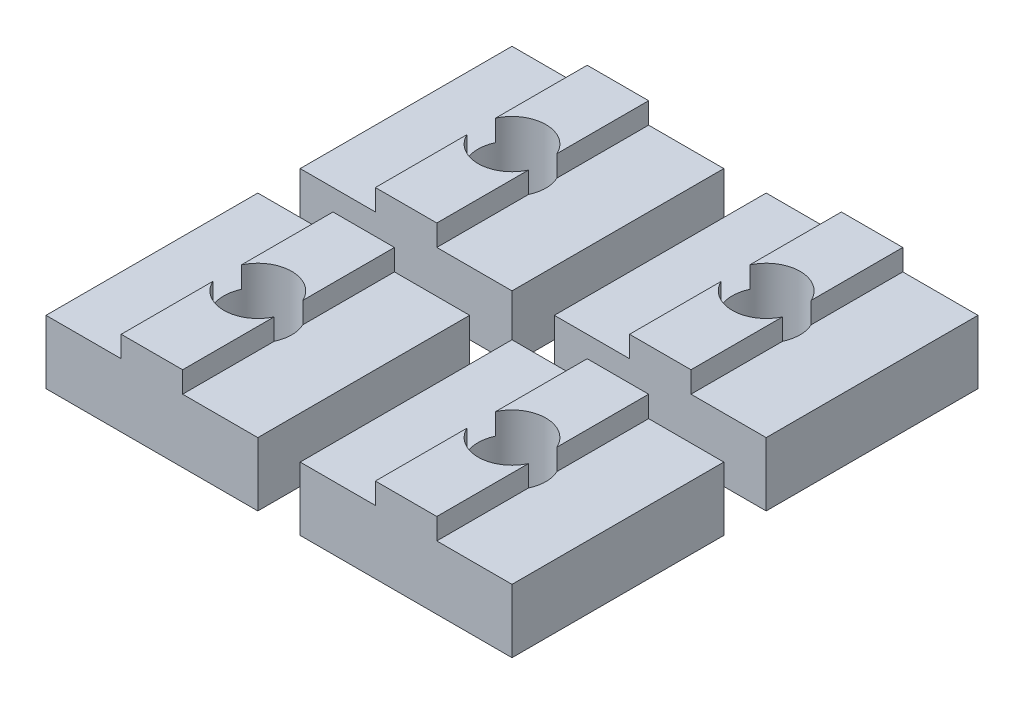
SolidWorks part; units mm, degrees
ref_plane "Front Plane" through (0, 0, 0) normal (0, 0, 1) x (1, 0, 0)
ref_plane "Top Plane" through (0, 0, 0) normal (0, 1, 0) x (1, 0, 0)
ref_plane "Right Plane" through (0, 0, 0) normal (1, 0, 0) x (0, 0, -1)
sketch "Esquisse1" plane through (0, 0, 0) normal (0, 0, 1) x (1, 0, 0)
  line L0 (-5, 0) -> (-5, 3)
  line L1 (-5, 3) -> (-1.45, 3)
  line L2 (-1.45, 3) -> (-1.45, 4)
  line L3 (-1.45, 4) -> (1.45, 4)
  line L4 (1.45, 4) -> (1.45, 3)
  line L5 (1.45, 3) -> (5, 3)
  line L6 (5, 3) -> (5, 0)
  line L7 (5, 0) -> (-5, 0)
  point P11 (0, 0)
  dimension "D1" = 10
  dimension "D2" = 3
  dimension "D3" = 1
  dimension "D4" = 2.9
  dimension "D5" = 3.55
extrude "Main" add sketch "Esquisse1" along normal blind 10
sketch "Esquisse2" plane through (0, 4, 0) normal (0, 1, 0) x (1, 0, 0)
  line L0 (0, -2.2) -> (0, 2.2) construction
  line L2 (-1.45, -10) -> (-5, -10) construction
  circle A1 centre (0, -5) radius 1.6
  dimension "D2" = 5
  dimension "D1" = 3.2
extrude "TopHole" cut sketch "Esquisse2" against normal through all
ref_axis "Axe1" through (-5.5, 0, 0) along (1, 0, 0)
pattern_linear "Répétition linéaire1" count 2 spacing 12 along (-1, 0, 0) of "TopHole", "Main"
pattern_linear "LPattern1" count 2 spacing 12 along (0, 0, 1) of bodies 102 103 109 108 107
